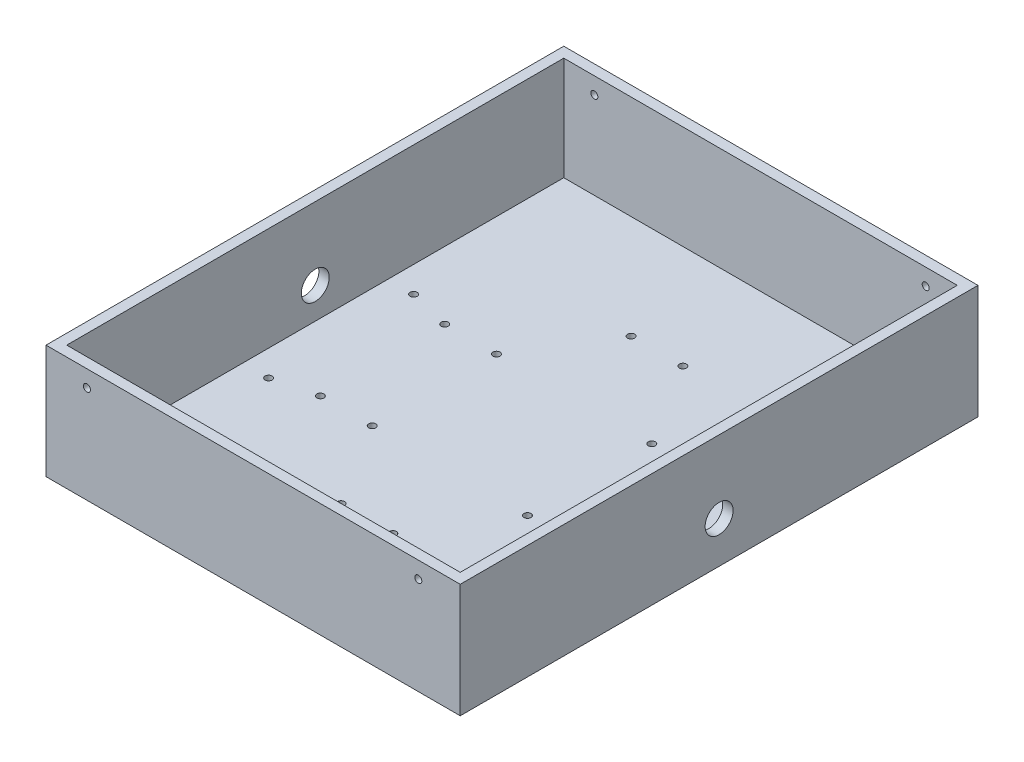
SolidWorks part; units mm, degrees
ref_plane "Front Plane" through (0, 0, 0) normal (0, 0, 1) x (1, 0, 0)
ref_plane "Top Plane" through (0, 0, 0) normal (0, 1, 0) x (1, 0, 0)
ref_plane "Right Plane" through (0, 0, 0) normal (1, 0, 0) x (0, 0, -1)
sketch "Sketch1" plane through (0, 0, 0) normal (0, 0, 1) x (1, 0, 0)
  line L0 (0, 50) -> (0, 0) construction
  line L1 (-95, 0) -> (95, 0)
  line L2 (-95, 0) -> (-95, 50)
  line L3 (-95, 50) -> (95, 50)
  line L4 (95, 0) -> (95, 50)
  dimension "D1" = 190
  dimension "D2" = 50
extrude "Boss-Extrude1" add sketch "Sketch1" along normal mid plane 240
shell "Shell1" thickness 5 removed face at (0, 50, 0) outward yes
sketch "Sketch2" plane through (0, 0, 0) normal (0, 1, 0) x (1, 0, 0)
  line L0 (-26.87, 0) -> (34.5029, 0) construction
  line L1 (0, -20.877) -> (0, 39.4378) construction
  circle A12 centre (-12.5, 70) radius 1.7
  circle A13 centre (-37.5, 30) radius 1.7
  circle A14 centre (-62.5, 30) radius 1.7
  circle A15 centre (-82.5, 35) radius 1.7
  circle A28 centre (82.5, 35) radius 1.7
  circle A29 centre (62.5, 30) radius 1.7
  circle A30 centre (37.5, 30) radius 1.7
  circle A31 centre (12.5, 70) radius 1.7
  circle A32 centre (12.5, -70) radius 1.7
  circle A33 centre (37.5, -30) radius 1.7
  circle A34 centre (62.5, -30) radius 1.7
  circle A35 centre (82.5, -35) radius 1.7
  circle A36 centre (-82.5, -35) radius 1.7
  circle A37 centre (-62.5, -30) radius 1.7
  circle A38 centre (-37.5, -30) radius 1.7
  circle A39 centre (-12.5, -70) radius 1.7
  dimension "D8" = 3.4
  dimension "D1" = 25
  dimension "D2" = 20
  dimension "D3" = 5
  dimension "D4" = 40
  dimension "D5" = 30
  dimension "D6" = 25
  dimension "D7" = 12.5
extrude "Cut-Extrude1" cut sketch "Sketch2" against normal through all both and the other way through all
sketch "Sketch3" plane through (0, 0, 0) normal (1, 0, 0) x (0, 0, -1)
  line L0 (-125, -5) -> (125, -5) construction
  circle A0 centre (0, 15) radius 6.75
  dimension "D2" = 13.5
  dimension "D1" = 20
extrude "Cut-Extrude2" cut sketch "Sketch3" against normal through all both and the other way through all
hole_wizard "M3 Clearance Hole1" positions "Sketch4" profile "Sketch5" hole size "M3" standard "ANSI Metric" end condition through all
sketch "Sketch4" plane through (0, 0, 125) normal (0, 0, 1) x (1, 0, 0)
  point P0 (-80.25, 42)
  point P1 (79.75, 42)
sketch "Sketch5" plane through (-80.25, 42, 125) normal (1, 0, 0) x (0, -1, 0)
  line L0 (0, 0) -> (0, 250)
  line L1 (0, 250) -> (1.7, 250)
  line L2 (1.7, 250) -> (1.7, 0)
  line L3 (1.7, 0) -> (0, 0)
  line L4 (0, -6.35) -> (0, 107.95) construction
  dimension "Thru Hole Dia." = 3.4
  dimension "Thru Hole Depth" = 250
